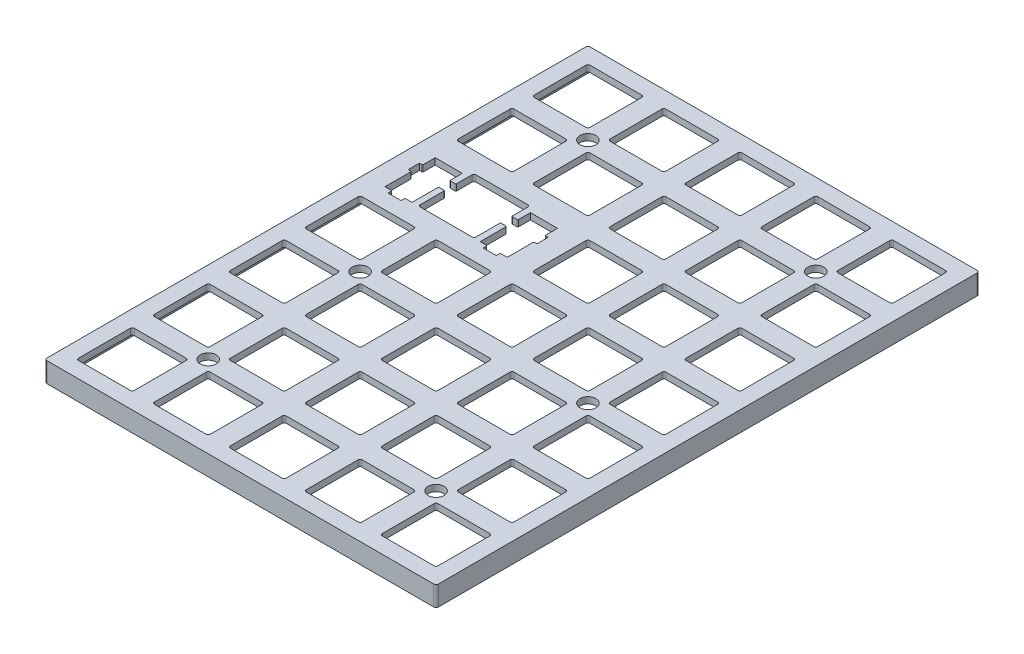
SolidWorks part; units mm, degrees
ref_plane "Front Plane" through (0, 0, 0) normal (0, 0, 1) x (1, 0, 0)
ref_plane "Top Plane" through (0, 0, 0) normal (0, 1, 0) x (1, 0, 0)
ref_plane "Right Plane" through (0, 0, 0) normal (1, 0, 0) x (0, 0, -1)
sketch "Sketch3" plane through (0, 0, 0) normal (0, 1, 0) x (1, 0, 0)
  line L0 (-104.5, -7) -> (-91.5, -7)
  line L1 (-91, -6.5) -> (-91, 6.5)
  line L2 (-91.5, 7) -> (-104.5, 7)
  line L3 (-105, 6.5) -> (-105, -6.5)
  line L4 (-85.45, -7) -> (-72.45, -7)
  line L5 (-71.95, -6.5) -> (-71.95, 6.5)
  line L6 (-72.45, 7) -> (-85.45, 7)
  line L7 (-85.95, 6.5) -> (-85.95, -6.5)
  line L8 (-66.4, -7) -> (-53.4, -7)
  line L9 (-52.9, -6.5) -> (-52.9, 6.5)
  line L10 (-53.4, 7) -> (-66.4, 7)
  line L11 (-66.9, 6.5) -> (-66.9, -6.5)
  line L12 (-47.35, -7) -> (-34.35, -7)
  line L13 (-33.85, -6.5) -> (-33.85, 6.5)
  line L14 (-34.35, 7) -> (-47.35, 7)
  line L15 (-47.85, 6.5) -> (-47.85, -6.5)
  line L16 (-28.3, -7) -> (-15.3, -7)
  line L17 (-14.8, -6.5) -> (-14.8, 6.5)
  line L18 (-15.3, 7) -> (-28.3, 7)
  line L19 (-28.8, 6.5) -> (-28.8, -6.5)
  line L20 (-104.5, -26.05) -> (-91.5, -26.05)
  line L21 (-91, -25.55) -> (-91, -12.55)
  line L22 (-91.5, -12.05) -> (-104.5, -12.05)
  line L23 (-105, -12.55) -> (-105, -25.55)
  line L24 (-85.45, -26.05) -> (-72.45, -26.05)
  line L25 (-71.95, -25.55) -> (-71.95, -12.55)
  line L26 (-72.45, -12.05) -> (-85.45, -12.05)
  line L27 (-85.95, -12.55) -> (-85.95, -25.55)
  line L28 (-66.4, -26.05) -> (-53.4, -26.05)
  line L29 (-52.9, -25.55) -> (-52.9, -12.55)
  line L30 (-53.4, -12.05) -> (-66.4, -12.05)
  line L31 (-66.9, -12.55) -> (-66.9, -25.55)
  line L32 (-47.35, -26.05) -> (-34.35, -26.05)
  line L33 (-33.85, -25.55) -> (-33.85, -12.55)
  line L34 (-34.35, -12.05) -> (-47.35, -12.05)
  line L35 (-47.85, -12.55) -> (-47.85, -25.55)
  line L36 (-28.3, -26.05) -> (-15.3, -26.05)
  line L37 (-14.8, -25.55) -> (-14.8, -12.55)
  line L38 (-15.3, -12.05) -> (-28.3, -12.05)
  line L39 (-28.8, -12.55) -> (-28.8, -25.55)
  line L40 (-104.5, -45.1) -> (-91.5, -45.1)
  line L41 (-91, -44.6) -> (-91, -31.6)
  line L42 (-91.5, -31.1) -> (-104.5, -31.1)
  line L43 (-105, -31.6) -> (-105, -44.6)
  line L44 (-85.45, -45.1) -> (-72.45, -45.1)
  line L45 (-71.95, -44.6) -> (-71.95, -31.6)
  line L46 (-72.45, -31.1) -> (-85.45, -31.1)
  line L47 (-85.95, -31.6) -> (-85.95, -44.6)
  line L48 (-66.4, -45.1) -> (-53.4, -45.1)
  line L49 (-52.9, -44.6) -> (-52.9, -31.6)
  line L50 (-53.4, -31.1) -> (-66.4, -31.1)
  line L51 (-66.9, -31.6) -> (-66.9, -44.6)
  line L52 (-47.35, -45.1) -> (-34.35, -45.1)
  line L53 (-33.85, -44.6) -> (-33.85, -31.6)
  line L54 (-34.35, -31.1) -> (-47.35, -31.1)
  line L55 (-47.85, -31.6) -> (-47.85, -44.6)
  line L56 (-28.3, -45.1) -> (-15.3, -45.1)
  line L57 (-14.8, -44.6) -> (-14.8, -31.6)
  line L58 (-15.3, -31.1) -> (-28.3, -31.1)
  line L59 (-28.8, -31.6) -> (-28.8, -44.6)
  line L60 (-94.975, -64.15) -> (-81.975, -64.15)
  line L61 (-81.475, -63.65) -> (-81.475, -50.65)
  line L62 (-81.975, -50.15) -> (-94.975, -50.15)
  line L63 (-95.475, -50.65) -> (-95.475, -63.65)
  line L64 (-66.4, -64.15) -> (-53.4, -64.15)
  line L65 (-52.9, -63.65) -> (-52.9, -50.65)
  line L66 (-53.4, -50.15) -> (-66.4, -50.15)
  line L67 (-66.9, -50.65) -> (-66.9, -63.65)
  line L68 (-47.35, -64.15) -> (-34.35, -64.15)
  line L69 (-33.85, -63.65) -> (-33.85, -50.65)
  line L70 (-34.35, -50.15) -> (-47.35, -50.15)
  line L71 (-47.85, -50.65) -> (-47.85, -63.65)
  line L72 (-28.3, -64.15) -> (-15.3, -64.15)
  line L73 (-14.8, -63.65) -> (-14.8, -50.65)
  line L74 (-15.3, -50.15) -> (-28.3, -50.15)
  line L75 (-28.8, -50.65) -> (-28.8, -63.65)
  line L76 (-104.5, -83.2) -> (-91.5, -83.2)
  line L77 (-91, -82.7) -> (-91, -69.7)
  line L78 (-91.5, -69.2) -> (-104.5, -69.2)
  line L79 (-105, -69.7) -> (-105, -82.7)
  line L80 (-85.45, -83.2) -> (-72.45, -83.2)
  line L81 (-71.95, -82.7) -> (-71.95, -69.7)
  line L82 (-72.45, -69.2) -> (-85.45, -69.2)
  line L83 (-85.95, -69.7) -> (-85.95, -82.7)
  line L84 (-66.4, -83.2) -> (-53.4, -83.2)
  line L85 (-52.9, -82.7) -> (-52.9, -69.7)
  line L86 (-53.4, -69.2) -> (-66.4, -69.2)
  line L87 (-66.9, -69.7) -> (-66.9, -82.7)
  line L88 (-47.35, -83.2) -> (-34.35, -83.2)
  line L89 (-33.85, -82.7) -> (-33.85, -69.7)
  line L90 (-34.35, -69.2) -> (-47.35, -69.2)
  line L91 (-47.85, -69.7) -> (-47.85, -82.7)
  line L92 (-28.3, -83.2) -> (-15.3, -83.2)
  line L93 (-14.8, -82.7) -> (-14.8, -69.7)
  line L94 (-15.3, -69.2) -> (-28.3, -69.2)
  line L95 (-28.8, -69.7) -> (-28.8, -82.7)
  line L96 (-104.5, -102.25) -> (-91.5, -102.25)
  line L97 (-91, -101.75) -> (-91, -88.75)
  line L98 (-91.5, -88.25) -> (-104.5, -88.25)
  line L99 (-105, -88.75) -> (-105, -101.75)
  line L100 (-85.45, -102.25) -> (-72.45, -102.25)
  line L101 (-71.95, -101.75) -> (-71.95, -88.75)
  line L102 (-72.45, -88.25) -> (-85.45, -88.25)
  line L103 (-85.95, -88.75) -> (-85.95, -101.75)
  line L104 (-66.4, -102.25) -> (-53.4, -102.25)
  line L105 (-52.9, -101.75) -> (-52.9, -88.75)
  line L106 (-53.4, -88.25) -> (-66.4, -88.25)
  line L107 (-66.9, -88.75) -> (-66.9, -101.75)
  line L108 (-47.35, -102.25) -> (-34.35, -102.25)
  line L109 (-33.85, -101.75) -> (-33.85, -88.75)
  line L110 (-34.35, -88.25) -> (-47.35, -88.25)
  line L111 (-47.85, -88.75) -> (-47.85, -101.75)
  line L112 (-28.3, -102.25) -> (-15.3, -102.25)
  line L113 (-14.8, -101.75) -> (-14.8, -88.75)
  line L114 (-15.3, -88.25) -> (-28.3, -88.25)
  line L115 (-28.8, -88.75) -> (-28.8, -101.75)
  line L116 (-104.5, -121.3) -> (-91.5, -121.3)
  line L117 (-91, -120.8) -> (-91, -107.8)
  line L118 (-91.5, -107.3) -> (-104.5, -107.3)
  line L119 (-105, -107.8) -> (-105, -120.8)
  line L120 (-85.45, -121.3) -> (-72.45, -121.3)
  line L121 (-71.95, -120.8) -> (-71.95, -107.8)
  line L122 (-72.45, -107.3) -> (-85.45, -107.3)
  line L123 (-85.95, -107.8) -> (-85.95, -120.8)
  line L124 (-66.4, -121.3) -> (-53.4, -121.3)
  line L125 (-52.9, -120.8) -> (-52.9, -107.8)
  line L126 (-53.4, -107.3) -> (-66.4, -107.3)
  line L127 (-66.9, -107.8) -> (-66.9, -120.8)
  line L128 (-47.35, -121.3) -> (-34.35, -121.3)
  line L129 (-33.85, -120.8) -> (-33.85, -107.8)
  line L130 (-34.35, -107.3) -> (-47.35, -107.3)
  line L131 (-47.85, -107.8) -> (-47.85, -120.8)
  line L132 (-28.3, -121.3) -> (-15.3, -121.3)
  line L133 (-14.8, -120.8) -> (-14.8, -107.8)
  line L134 (-15.3, -107.3) -> (-28.3, -107.3)
  line L135 (-28.8, -107.8) -> (-28.8, -120.8)
  line L136 (-104.5, -140.35) -> (-91.5, -140.35)
  line L137 (-91, -139.85) -> (-91, -126.85)
  line L138 (-91.5, -126.35) -> (-104.5, -126.35)
  line L139 (-105, -126.85) -> (-105, -139.85)
  line L140 (-85.45, -140.35) -> (-72.45, -140.35)
  line L141 (-71.95, -139.85) -> (-71.95, -126.85)
  line L142 (-72.45, -126.35) -> (-85.45, -126.35)
  line L143 (-85.95, -126.85) -> (-85.95, -139.85)
  line L144 (-66.4, -140.35) -> (-53.4, -140.35)
  line L145 (-52.9, -139.85) -> (-52.9, -126.85)
  line L146 (-53.4, -126.35) -> (-66.4, -126.35)
  line L147 (-66.9, -126.85) -> (-66.9, -139.85)
  line L148 (-47.35, -140.35) -> (-34.35, -140.35)
  line L149 (-33.85, -139.85) -> (-33.85, -126.85)
  line L150 (-34.35, -126.35) -> (-47.35, -126.35)
  line L151 (-47.85, -126.85) -> (-47.85, -139.85)
  line L152 (-28.3, -140.35) -> (-15.3, -140.35)
  line L153 (-14.8, -139.85) -> (-14.8, -126.85)
  line L154 (-15.3, -126.35) -> (-28.3, -126.35)
  line L155 (-28.8, -126.85) -> (-28.8, -139.85)
  line L156 (-103.413, -66.15) -> (-97.413, -66.15)
  line L157 (-96.913, -65.65) -> (-96.913, -51.65)
  line L158 (-97.413, -51.15) -> (-103.413, -51.15)
  line L159 (-103.913, -51.65) -> (-103.913, -65.65)
  line L160 (-79.537, -66.15) -> (-73.537, -66.15)
  line L161 (-73.037, -65.65) -> (-73.037, -51.65)
  line L162 (-73.537, -51.15) -> (-79.537, -51.15)
  line L163 (-80.037, -51.65) -> (-80.037, -65.65)
  line L165 (-109, 11) -> (-10.8, 11)
  line L166 (-109, 11) -> (-109, -144.35)
  line L167 (-109, -144.35) -> (-10.8, -144.35)
  line L168 (-10.8, 11) -> (-10.8, -144.35)
  arc A0 (-105, -6.5) -> (-104.5, -7) centre (-104.5, -6.5) ccw
  arc A1 (-91.5, -7) -> (-91, -6.5) centre (-91.5, -6.5) ccw
  arc A2 (-91, 6.5) -> (-91.5, 7) centre (-91.5, 6.5) ccw
  arc A3 (-104.5, 7) -> (-105, 6.5) centre (-104.5, 6.5) ccw
  arc A4 (-85.95, -6.5) -> (-85.45, -7) centre (-85.45, -6.5) ccw
  arc A5 (-72.45, -7) -> (-71.95, -6.5) centre (-72.45, -6.5) ccw
  arc A6 (-71.95, 6.5) -> (-72.45, 7) centre (-72.45, 6.5) ccw
  arc A7 (-85.45, 7) -> (-85.95, 6.5) centre (-85.45, 6.5) ccw
  arc A8 (-66.9, -6.5) -> (-66.4, -7) centre (-66.4, -6.5) ccw
  arc A9 (-53.4, -7) -> (-52.9, -6.5) centre (-53.4, -6.5) ccw
  arc A10 (-52.9, 6.5) -> (-53.4, 7) centre (-53.4, 6.5) ccw
  arc A11 (-66.4, 7) -> (-66.9, 6.5) centre (-66.4, 6.5) ccw
  arc A12 (-47.85, -6.5) -> (-47.35, -7) centre (-47.35, -6.5) ccw
  arc A13 (-34.35, -7) -> (-33.85, -6.5) centre (-34.35, -6.5) ccw
  arc A14 (-33.85, 6.5) -> (-34.35, 7) centre (-34.35, 6.5) ccw
  arc A15 (-47.35, 7) -> (-47.85, 6.5) centre (-47.35, 6.5) ccw
  arc A16 (-28.8, -6.5) -> (-28.3, -7) centre (-28.3, -6.5) ccw
  arc A17 (-15.3, -7) -> (-14.8, -6.5) centre (-15.3, -6.5) ccw
  arc A18 (-14.8, 6.5) -> (-15.3, 7) centre (-15.3, 6.5) ccw
  arc A19 (-28.3, 7) -> (-28.8, 6.5) centre (-28.3, 6.5) ccw
  arc A20 (-105, -25.55) -> (-104.5, -26.05) centre (-104.5, -25.55) ccw
  arc A21 (-91.5, -26.05) -> (-91, -25.55) centre (-91.5, -25.55) ccw
  arc A22 (-91, -12.55) -> (-91.5, -12.05) centre (-91.5, -12.55) ccw
  arc A23 (-104.5, -12.05) -> (-105, -12.55) centre (-104.5, -12.55) ccw
  arc A24 (-85.95, -25.55) -> (-85.45, -26.05) centre (-85.45, -25.55) ccw
  arc A25 (-72.45, -26.05) -> (-71.95, -25.55) centre (-72.45, -25.55) ccw
  arc A26 (-71.95, -12.55) -> (-72.45, -12.05) centre (-72.45, -12.55) ccw
  arc A27 (-85.45, -12.05) -> (-85.95, -12.55) centre (-85.45, -12.55) ccw
  arc A28 (-66.9, -25.55) -> (-66.4, -26.05) centre (-66.4, -25.55) ccw
  arc A29 (-53.4, -26.05) -> (-52.9, -25.55) centre (-53.4, -25.55) ccw
  arc A30 (-52.9, -12.55) -> (-53.4, -12.05) centre (-53.4, -12.55) ccw
  arc A31 (-66.4, -12.05) -> (-66.9, -12.55) centre (-66.4, -12.55) ccw
  arc A32 (-47.85, -25.55) -> (-47.35, -26.05) centre (-47.35, -25.55) ccw
  arc A33 (-34.35, -26.05) -> (-33.85, -25.55) centre (-34.35, -25.55) ccw
  arc A34 (-33.85, -12.55) -> (-34.35, -12.05) centre (-34.35, -12.55) ccw
  arc A35 (-47.35, -12.05) -> (-47.85, -12.55) centre (-47.35, -12.55) ccw
  arc A36 (-28.8, -25.55) -> (-28.3, -26.05) centre (-28.3, -25.55) ccw
  arc A37 (-15.3, -26.05) -> (-14.8, -25.55) centre (-15.3, -25.55) ccw
  arc A38 (-14.8, -12.55) -> (-15.3, -12.05) centre (-15.3, -12.55) ccw
  arc A39 (-28.3, -12.05) -> (-28.8, -12.55) centre (-28.3, -12.55) ccw
  arc A40 (-105, -44.6) -> (-104.5, -45.1) centre (-104.5, -44.6) ccw
  arc A41 (-91.5, -45.1) -> (-91, -44.6) centre (-91.5, -44.6) ccw
  arc A42 (-91, -31.6) -> (-91.5, -31.1) centre (-91.5, -31.6) ccw
  arc A43 (-104.5, -31.1) -> (-105, -31.6) centre (-104.5, -31.6) ccw
  arc A44 (-85.95, -44.6) -> (-85.45, -45.1) centre (-85.45, -44.6) ccw
  arc A45 (-72.45, -45.1) -> (-71.95, -44.6) centre (-72.45, -44.6) ccw
  arc A46 (-71.95, -31.6) -> (-72.45, -31.1) centre (-72.45, -31.6) ccw
  arc A47 (-85.45, -31.1) -> (-85.95, -31.6) centre (-85.45, -31.6) ccw
  arc A48 (-66.9, -44.6) -> (-66.4, -45.1) centre (-66.4, -44.6) ccw
  arc A49 (-53.4, -45.1) -> (-52.9, -44.6) centre (-53.4, -44.6) ccw
  arc A50 (-52.9, -31.6) -> (-53.4, -31.1) centre (-53.4, -31.6) ccw
  arc A51 (-66.4, -31.1) -> (-66.9, -31.6) centre (-66.4, -31.6) ccw
  arc A52 (-47.85, -44.6) -> (-47.35, -45.1) centre (-47.35, -44.6) ccw
  arc A53 (-34.35, -45.1) -> (-33.85, -44.6) centre (-34.35, -44.6) ccw
  arc A54 (-33.85, -31.6) -> (-34.35, -31.1) centre (-34.35, -31.6) ccw
  arc A55 (-47.35, -31.1) -> (-47.85, -31.6) centre (-47.35, -31.6) ccw
  arc A56 (-28.8, -44.6) -> (-28.3, -45.1) centre (-28.3, -44.6) ccw
  arc A57 (-15.3, -45.1) -> (-14.8, -44.6) centre (-15.3, -44.6) ccw
  arc A58 (-14.8, -31.6) -> (-15.3, -31.1) centre (-15.3, -31.6) ccw
  arc A59 (-28.3, -31.1) -> (-28.8, -31.6) centre (-28.3, -31.6) ccw
  arc A60 (-95.475, -63.65) -> (-94.975, -64.15) centre (-94.975, -63.65) ccw
  arc A61 (-81.975, -64.15) -> (-81.475, -63.65) centre (-81.975, -63.65) ccw
  arc A62 (-81.475, -50.65) -> (-81.975, -50.15) centre (-81.975, -50.65) ccw
  arc A63 (-94.975, -50.15) -> (-95.475, -50.65) centre (-94.975, -50.65) ccw
  arc A64 (-66.9, -63.65) -> (-66.4, -64.15) centre (-66.4, -63.65) ccw
  arc A65 (-53.4, -64.15) -> (-52.9, -63.65) centre (-53.4, -63.65) ccw
  arc A66 (-52.9, -50.65) -> (-53.4, -50.15) centre (-53.4, -50.65) ccw
  arc A67 (-66.4, -50.15) -> (-66.9, -50.65) centre (-66.4, -50.65) ccw
  arc A68 (-47.85, -63.65) -> (-47.35, -64.15) centre (-47.35, -63.65) ccw
  arc A69 (-34.35, -64.15) -> (-33.85, -63.65) centre (-34.35, -63.65) ccw
  arc A70 (-33.85, -50.65) -> (-34.35, -50.15) centre (-34.35, -50.65) ccw
  arc A71 (-47.35, -50.15) -> (-47.85, -50.65) centre (-47.35, -50.65) ccw
  arc A72 (-28.8, -63.65) -> (-28.3, -64.15) centre (-28.3, -63.65) ccw
  arc A73 (-15.3, -64.15) -> (-14.8, -63.65) centre (-15.3, -63.65) ccw
  arc A74 (-14.8, -50.65) -> (-15.3, -50.15) centre (-15.3, -50.65) ccw
  arc A75 (-28.3, -50.15) -> (-28.8, -50.65) centre (-28.3, -50.65) ccw
  arc A76 (-105, -82.7) -> (-104.5, -83.2) centre (-104.5, -82.7) ccw
  arc A77 (-91.5, -83.2) -> (-91, -82.7) centre (-91.5, -82.7) ccw
  arc A78 (-91, -69.7) -> (-91.5, -69.2) centre (-91.5, -69.7) ccw
  arc A79 (-104.5, -69.2) -> (-105, -69.7) centre (-104.5, -69.7) ccw
  arc A80 (-85.95, -82.7) -> (-85.45, -83.2) centre (-85.45, -82.7) ccw
  arc A81 (-72.45, -83.2) -> (-71.95, -82.7) centre (-72.45, -82.7) ccw
  arc A82 (-71.95, -69.7) -> (-72.45, -69.2) centre (-72.45, -69.7) ccw
  arc A83 (-85.45, -69.2) -> (-85.95, -69.7) centre (-85.45, -69.7) ccw
  arc A84 (-66.9, -82.7) -> (-66.4, -83.2) centre (-66.4, -82.7) ccw
  arc A85 (-53.4, -83.2) -> (-52.9, -82.7) centre (-53.4, -82.7) ccw
  arc A86 (-52.9, -69.7) -> (-53.4, -69.2) centre (-53.4, -69.7) ccw
  arc A87 (-66.4, -69.2) -> (-66.9, -69.7) centre (-66.4, -69.7) ccw
  arc A88 (-47.85, -82.7) -> (-47.35, -83.2) centre (-47.35, -82.7) ccw
  arc A89 (-34.35, -83.2) -> (-33.85, -82.7) centre (-34.35, -82.7) ccw
  arc A90 (-33.85, -69.7) -> (-34.35, -69.2) centre (-34.35, -69.7) ccw
  arc A91 (-47.35, -69.2) -> (-47.85, -69.7) centre (-47.35, -69.7) ccw
  arc A92 (-28.8, -82.7) -> (-28.3, -83.2) centre (-28.3, -82.7) ccw
  arc A93 (-15.3, -83.2) -> (-14.8, -82.7) centre (-15.3, -82.7) ccw
  arc A94 (-14.8, -69.7) -> (-15.3, -69.2) centre (-15.3, -69.7) ccw
  arc A95 (-28.3, -69.2) -> (-28.8, -69.7) centre (-28.3, -69.7) ccw
  arc A96 (-105, -101.75) -> (-104.5, -102.25) centre (-104.5, -101.75) ccw
  arc A97 (-91.5, -102.25) -> (-91, -101.75) centre (-91.5, -101.75) ccw
  arc A98 (-91, -88.75) -> (-91.5, -88.25) centre (-91.5, -88.75) ccw
  arc A99 (-104.5, -88.25) -> (-105, -88.75) centre (-104.5, -88.75) ccw
  arc A100 (-85.95, -101.75) -> (-85.45, -102.25) centre (-85.45, -101.75) ccw
  arc A101 (-72.45, -102.25) -> (-71.95, -101.75) centre (-72.45, -101.75) ccw
  arc A102 (-71.95, -88.75) -> (-72.45, -88.25) centre (-72.45, -88.75) ccw
  arc A103 (-85.45, -88.25) -> (-85.95, -88.75) centre (-85.45, -88.75) ccw
  arc A104 (-66.9, -101.75) -> (-66.4, -102.25) centre (-66.4, -101.75) ccw
  arc A105 (-53.4, -102.25) -> (-52.9, -101.75) centre (-53.4, -101.75) ccw
  arc A106 (-52.9, -88.75) -> (-53.4, -88.25) centre (-53.4, -88.75) ccw
  arc A107 (-66.4, -88.25) -> (-66.9, -88.75) centre (-66.4, -88.75) ccw
  arc A108 (-47.85, -101.75) -> (-47.35, -102.25) centre (-47.35, -101.75) ccw
  arc A109 (-34.35, -102.25) -> (-33.85, -101.75) centre (-34.35, -101.75) ccw
  arc A110 (-33.85, -88.75) -> (-34.35, -88.25) centre (-34.35, -88.75) ccw
  arc A111 (-47.35, -88.25) -> (-47.85, -88.75) centre (-47.35, -88.75) ccw
  arc A112 (-28.8, -101.75) -> (-28.3, -102.25) centre (-28.3, -101.75) ccw
  arc A113 (-15.3, -102.25) -> (-14.8, -101.75) centre (-15.3, -101.75) ccw
  arc A114 (-14.8, -88.75) -> (-15.3, -88.25) centre (-15.3, -88.75) ccw
  arc A115 (-28.3, -88.25) -> (-28.8, -88.75) centre (-28.3, -88.75) ccw
  arc A116 (-105, -120.8) -> (-104.5, -121.3) centre (-104.5, -120.8) ccw
  arc A117 (-91.5, -121.3) -> (-91, -120.8) centre (-91.5, -120.8) ccw
  arc A118 (-91, -107.8) -> (-91.5, -107.3) centre (-91.5, -107.8) ccw
  arc A119 (-104.5, -107.3) -> (-105, -107.8) centre (-104.5, -107.8) ccw
  arc A120 (-85.95, -120.8) -> (-85.45, -121.3) centre (-85.45, -120.8) ccw
  arc A121 (-72.45, -121.3) -> (-71.95, -120.8) centre (-72.45, -120.8) ccw
  arc A122 (-71.95, -107.8) -> (-72.45, -107.3) centre (-72.45, -107.8) ccw
  arc A123 (-85.45, -107.3) -> (-85.95, -107.8) centre (-85.45, -107.8) ccw
  arc A124 (-66.9, -120.8) -> (-66.4, -121.3) centre (-66.4, -120.8) ccw
  arc A125 (-53.4, -121.3) -> (-52.9, -120.8) centre (-53.4, -120.8) ccw
  arc A126 (-52.9, -107.8) -> (-53.4, -107.3) centre (-53.4, -107.8) ccw
  arc A127 (-66.4, -107.3) -> (-66.9, -107.8) centre (-66.4, -107.8) ccw
  arc A128 (-47.85, -120.8) -> (-47.35, -121.3) centre (-47.35, -120.8) ccw
  arc A129 (-34.35, -121.3) -> (-33.85, -120.8) centre (-34.35, -120.8) ccw
  arc A130 (-33.85, -107.8) -> (-34.35, -107.3) centre (-34.35, -107.8) ccw
  arc A131 (-47.35, -107.3) -> (-47.85, -107.8) centre (-47.35, -107.8) ccw
  arc A132 (-28.8, -120.8) -> (-28.3, -121.3) centre (-28.3, -120.8) ccw
  arc A133 (-15.3, -121.3) -> (-14.8, -120.8) centre (-15.3, -120.8) ccw
  arc A134 (-14.8, -107.8) -> (-15.3, -107.3) centre (-15.3, -107.8) ccw
  arc A135 (-28.3, -107.3) -> (-28.8, -107.8) centre (-28.3, -107.8) ccw
  arc A136 (-105, -139.85) -> (-104.5, -140.35) centre (-104.5, -139.85) ccw
  arc A137 (-91.5, -140.35) -> (-91, -139.85) centre (-91.5, -139.85) ccw
  arc A138 (-91, -126.85) -> (-91.5, -126.35) centre (-91.5, -126.85) ccw
  arc A139 (-104.5, -126.35) -> (-105, -126.85) centre (-104.5, -126.85) ccw
  arc A140 (-85.95, -139.85) -> (-85.45, -140.35) centre (-85.45, -139.85) ccw
  arc A141 (-72.45, -140.35) -> (-71.95, -139.85) centre (-72.45, -139.85) ccw
  arc A142 (-71.95, -126.85) -> (-72.45, -126.35) centre (-72.45, -126.85) ccw
  arc A143 (-85.45, -126.35) -> (-85.95, -126.85) centre (-85.45, -126.85) ccw
  arc A144 (-66.9, -139.85) -> (-66.4, -140.35) centre (-66.4, -139.85) ccw
  arc A145 (-53.4, -140.35) -> (-52.9, -139.85) centre (-53.4, -139.85) ccw
  arc A146 (-52.9, -126.85) -> (-53.4, -126.35) centre (-53.4, -126.85) ccw
  arc A147 (-66.4, -126.35) -> (-66.9, -126.85) centre (-66.4, -126.85) ccw
  arc A148 (-47.85, -139.85) -> (-47.35, -140.35) centre (-47.35, -139.85) ccw
  arc A149 (-34.35, -140.35) -> (-33.85, -139.85) centre (-34.35, -139.85) ccw
  arc A150 (-33.85, -126.85) -> (-34.35, -126.35) centre (-34.35, -126.85) ccw
  arc A151 (-47.35, -126.35) -> (-47.85, -126.85) centre (-47.35, -126.85) ccw
  arc A152 (-28.8, -139.85) -> (-28.3, -140.35) centre (-28.3, -139.85) ccw
  arc A153 (-15.3, -140.35) -> (-14.8, -139.85) centre (-15.3, -139.85) ccw
  arc A154 (-14.8, -126.85) -> (-15.3, -126.35) centre (-15.3, -126.85) ccw
  arc A155 (-28.3, -126.35) -> (-28.8, -126.85) centre (-28.3, -126.85) ccw
  arc A156 (-103.913, -65.65) -> (-103.413, -66.15) centre (-103.413, -65.65) ccw
  arc A157 (-97.413, -66.15) -> (-96.913, -65.65) centre (-97.413, -65.65) ccw
  arc A158 (-96.913, -51.65) -> (-97.413, -51.15) centre (-97.413, -51.65) ccw
  arc A159 (-103.413, -51.15) -> (-103.913, -51.65) centre (-103.413, -51.65) ccw
  arc A160 (-80.037, -65.65) -> (-79.537, -66.15) centre (-79.537, -65.65) ccw
  arc A161 (-73.537, -66.15) -> (-73.037, -65.65) centre (-73.537, -65.65) ccw
  arc A162 (-73.037, -51.65) -> (-73.537, -51.15) centre (-73.537, -51.65) ccw
  arc A163 (-79.537, -51.15) -> (-80.037, -51.65) centre (-79.537, -51.65) ccw
  dimension "D1" = 4
  dimension "D2" = 4
  dimension "D3" = 4
  dimension "D4" = 4
  dimension "D5" = 98.2
extrude "Boss-Extrude2" add sketch "Sketch3" along normal blind 1.6 separate body
sketch "Sketch4" plane through (0, 1.6, 0) normal (0, 1, 0) x (1, 0, 0)
  line L0 (-10.8, -144.35) -> (-10.8, 11) construction
  line L1 (-104.5, -26.05) -> (-104.5, -31.1) construction
  line L2 (-104.5, -83.2) -> (-104.5, -88.25) construction
  line L3 (-104.5, -121.3) -> (-104.5, -126.35) construction
  line L4 (-91, 6.5) -> (-85.95, 6.5) construction
  line L5 (-33.85, 6.5) -> (-28.8, 6.5) construction
  line L6 (-104.5, -26.05) -> (-91.5, -26.05) construction
  line L7 (-15.3, -12.05) -> (-28.3, -12.05) construction
  line L8 (-109, 11) -> (-10.8, 11)
  line L9 (-109, 11) -> (-109, -8.05)
  line L10 (-109, -8.05) -> (-10.8, -8.05)
  line L11 (-10.8, 11) -> (-10.8, -8.05)
  circle A0 centre (-88.475, -28.575) radius 2
  circle A1 centre (-31.325, -28.575) radius 2
  circle A2 centre (-88.475, -85.725) radius 2
  circle A3 centre (-31.325, -85.725) radius 2
  circle A4 centre (-88.475, -123.825) radius 2
  circle A5 centre (-31.325, -123.825) radius 2
  point P28 (-104.5, -123.825)
  point P29 (-104.5, -85.725)
  point P30 (-104.5, -28.575)
  point P39 (-31.325, 6.5)
  point P40 (-88.475, 6.5)
  dimension "D2" = 4
  dimension "D1" = 98.2
  dimension "D3" = 4
extrude "Cut-Extrude2" cut sketch "Sketch4" against normal blind 10
sketch "Sketch6" plane through (0, 1.6, 0) normal (0, 1, 0) x (1, 0, 0)
  line L1 (-96.577, -48.5256) -> (-105.5128, -48.5256)
  line L2 (-96.577, -48.5256) -> (-96.577, -67.4642)
  line L3 (-96.577, -67.4642) -> (-105.5128, -67.4642)
  line L4 (-105.5128, -48.5256) -> (-105.5128, -67.4642)
  line L5 (-80.4391, -48.5256) -> (-71.2393, -48.5256)
  line L6 (-80.4391, -48.5256) -> (-80.4391, -67.0484)
  line L7 (-80.4391, -67.0484) -> (-71.2393, -67.0484)
  line L8 (-71.2393, -48.5256) -> (-71.2393, -67.0484)
  point P9 (-80.037, -51.65)
  point P10 (-80.037, -51.65)
  point P11 (-71.2393, -67.0484)
extrude "Boss-Extrude3" add sketch "Sketch6" against normal up to surface (1.6 mm away) up to face at (-88.475, 0, 125.825)
sketch "Sketch7" plane through (0, 1.6, 0) normal (0, 1, 0) x (1, 0, 0)
  line L0 (-95.475, -54.7) -> (-97.015, -54.7)
  line L1 (-95.475, -50.65) -> (-95.475, -63.65) construction
  line L2 (-97.015, -54.7) -> (-97.015, -51.55)
  line L3 (-97.015, -51.55) -> (-103.815, -51.55)
  line L4 (-103.815, -51.55) -> (-103.815, -54.7)
  line L5 (-103.815, -54.7) -> (-104.615, -54.7)
  line L6 (-104.615, -54.7) -> (-104.615, -57.5)
  line L7 (-104.615, -57.5) -> (-103.815, -57.5)
  line L8 (-103.815, -57.5) -> (-103.815, -64.15)
  line L9 (-103.815, -64.15) -> (-102.065, -64.15)
  line L10 (-102.065, -64.15) -> (-102.065, -65.15)
  line L11 (-102.065, -65.15) -> (-98.765, -65.15)
  line L12 (-98.765, -65.15) -> (-98.765, -64.15)
  line L13 (-98.765, -64.15) -> (-97.015, -64.15)
  line L14 (-97.015, -64.15) -> (-97.015, -57.5)
  line L15 (-97.015, -57.5) -> (-95.475, -57.5)
  line L16 (-95.475, -57.5) -> (-95.475, -54.7)
  line L17 (-81.475, -54.7) -> (-79.935, -54.7)
  line L18 (-81.475, -63.65) -> (-81.475, -50.65) construction
  line L19 (-79.935, -54.7) -> (-79.935, -51.55)
  line L20 (-79.935, -51.55) -> (-73.135, -51.55)
  line L21 (-73.135, -51.55) -> (-73.135, -54.7)
  line L22 (-73.135, -54.7) -> (-72.335, -54.7)
  line L23 (-72.335, -54.7) -> (-72.335, -57.5)
  line L24 (-72.335, -57.5) -> (-73.135, -57.5)
  line L25 (-73.135, -57.5) -> (-73.135, -64.15)
  line L26 (-73.135, -64.15) -> (-74.885, -64.15)
  line L27 (-74.885, -64.15) -> (-74.885, -65.15)
  line L28 (-74.885, -65.15) -> (-78.185, -65.15)
  line L29 (-78.185, -65.15) -> (-78.185, -64.15)
  line L30 (-78.185, -64.15) -> (-79.935, -64.15)
  line L31 (-79.935, -64.15) -> (-79.935, -57.5)
  line L32 (-79.935, -57.5) -> (-81.475, -57.5)
  line L33 (-81.975, -50.15) -> (-94.975, -50.15) construction
  line L34 (-81.475, -54.7) -> (-81.475, -57.5)
  point P4 (-100.415, -51.55)
  point P23 (-76.535, -51.55)
  point P38 (-76.535, -65.15)
  point P39 (-95.475, -57.15)
  point P40 (-100.415, -65.15)
  point P42 (-88.475, -50.15)
  dimension "D1" = 23.88
  dimension "D2" = 13.6
  dimension "D3" = 12.6
  dimension "D4" = 6.8
  dimension "D5" = 6.8
  dimension "D6" = 3.3
  dimension "D7" = 3.3
  dimension "D8" = 4.2
  dimension "D9" = 4.2
  dimension "D10" = 11.94
  dimension "D11" = 2.8
  dimension "D12" = 0.35
  dimension "D13" = 5.95
extrude "Cut-Extrude3" cut sketch "Sketch7" against normal blind 10
fillet "Fillet1" radius 0.2 16 edges at (-81.475, 0.8, 54.7) (-97.015, 0.8, 54.7) (-95.475, 0.8, 54.7) (-79.935, 0.8, 54.7) (-73.135, 0.8, 54.7) (-74.885, 0.8, 64.15) (-78.185, 0.8, 64.15) (-73.135, 0.8, 57.5) (-79.935, 0.8, 57.5) (-81.475, 0.8, 57.5) (-95.475, 0.8, 57.5) (-97.015, 0.8, 57.5) (-98.765, 0.8, 64.15) (-102.065, 0.8, 64.15) (-103.815, 0.8, 57.5) (-103.815, 0.8, 54.7)
sketch "Sketch8" plane through (0, 0, 0) normal (0, -1, 0) x (1, 0, 0)
  line L0 (-108, 8.05) -> (-108, 143.35)
  line L1 (-109, 8.05) -> (-10.8, 8.05) construction
  line L2 (-108, 143.35) -> (-11.8, 143.35)
  line L3 (-11.8, 143.35) -> (-11.8, 8.05)
  line L4 (-11.8, 8.05) -> (-10.8, 8.05)
  line L5 (-10.8, 8.05) -> (-10.8, 144.35)
  line L6 (-10.8, 144.35) -> (-109, 144.35)
  line L7 (-109, 144.35) -> (-109, 8.05)
  line L8 (-109, 8.05) -> (-108, 8.05)
  dimension "D1" = 1
  dimension "D2" = 1
  dimension "D3" = 1
extrude "Boss-Extrude4" add sketch "Sketch8" along normal blind 3.4
fillet "Fillet2" radius 1.6 2 edges at (-11.8, -1.7, 143.35) (-108, -1.7, 143.35)
fillet "Fillet3" radius 0.6 4 edges at (-10.8, -0.9, 8.05) (-109, -0.9, 8.05) (-10.8, -0.9, 144.35) (-109, -0.9, 144.35)
equation "\"d\"=4"
